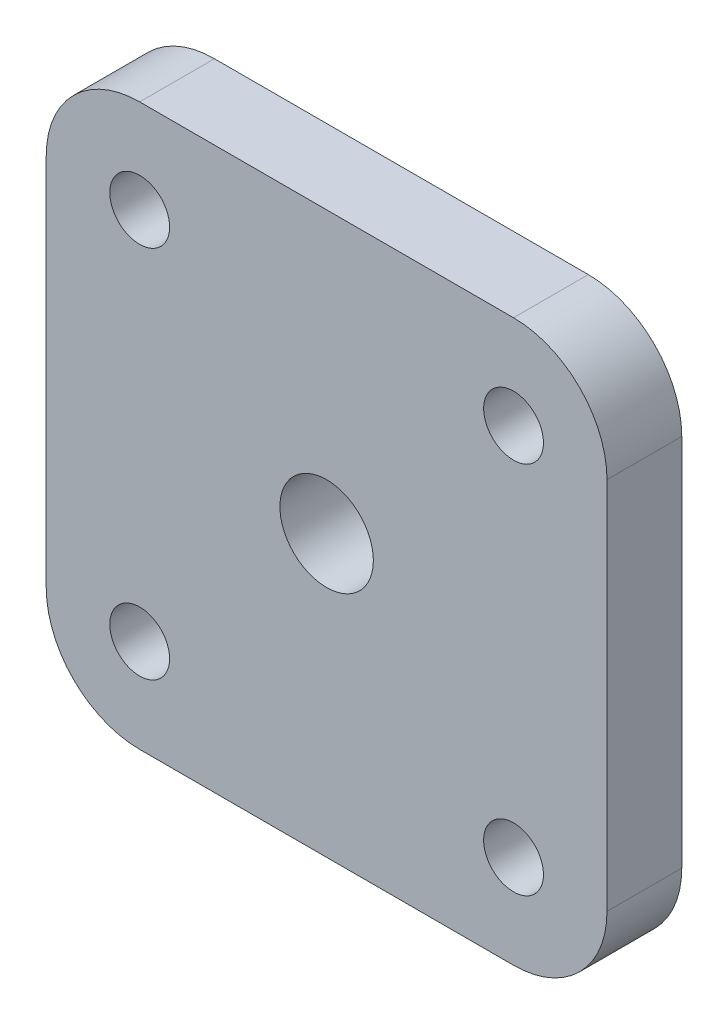
SolidWorks part; units mm, degrees
ref_plane "Front Plane" through (0, 0, 0) normal (0, 0, 1) x (1, 0, 0)
ref_plane "Top Plane" through (0, 0, 0) normal (0, 1, 0) x (1, 0, 0)
ref_plane "Right Plane" through (0, 0, 0) normal (1, 0, 0) x (0, 0, -1)
sketch "Sketch1" plane through (0, 0, 0) normal (0, 0, 1) x (1, 0, 0)
  line L1 (15, 15) -> (-15, 15)
  line L2 (15, 15) -> (15, -15)
  line L3 (15, -15) -> (-15, -15)
  line L4 (-15, 15) -> (-15, -15)
  line L5 (15, 15) -> (-15, -15) construction
  line L6 (15, -15) -> (-15, 15) construction
  point P0 (0, 0)
  dimension "D1" = 30
  dimension "D2" = 30
extrude "Boss-Extrude1" add sketch "Sketch1" along normal blind 4
sketch "Sketch2" plane through (0, 0, 4) normal (0, 0, 1) x (1, 0, 0)
  circle A0 centre (0, 0) radius 2.5
  dimension "D1" = 5
sketch "Sketch3" plane through (0, 0, 4) normal (0, 0, 1) x (1, 0, 0)
  line L1 (10, 10) -> (-10, 10) construction
  line L2 (10, 10) -> (10, -10) construction
  line L3 (10, -10) -> (-10, -10) construction
  line L4 (-10, 10) -> (-10, -10) construction
  line L5 (10, 10) -> (-10, -10) construction
  line L6 (10, -10) -> (-10, 10) construction
  circle A0 centre (-10, 10) radius 1.6
  circle A1 centre (10, 10) radius 1.6
  circle A2 centre (10, -10) radius 1.6
  circle A3 centre (-10, -10) radius 1.6
  point P0 (0, 0)
  dimension "D3" = 3.2
  dimension "D1" = 20
extrude "Dowel cut" cut sketch "Sketch3" against normal through all
extrude "Screw cut" cut sketch "Sketch2" against normal through all
fillet "Fillet1" radius 5 4 edges at (15, -15, 2) (-15, -15, 2) (-15, 15, 2) (15, 15, 2)
